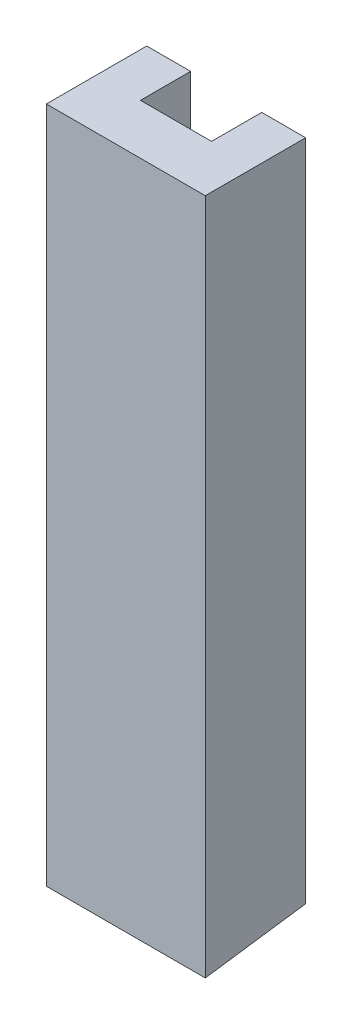
SolidWorks part; units mm, degrees
ref_plane "Front Plane" through (0, 0, 0) normal (0, 0, 1) x (1, 0, 0)
ref_plane "Top Plane" through (0, 0, 0) normal (0, 1, 0) x (1, 0, 0)
ref_plane "Right Plane" through (0, 0, 0) normal (1, 0, 0) x (0, 0, -1)
sketch "Sketch1" plane through (0, 0, 0) normal (0, 0, 1) x (1, 0, 0)
  line L1 (-9.7143, 13.1912) -> (9.2857, 13.1912)
  line L2 (-9.7143, 13.1912) -> (-9.7143, -67.8088)
  line L3 (-9.7143, -67.8088) -> (9.2857, -67.8088)
  line L4 (9.2857, 13.1912) -> (9.2857, -67.8088)
  dimension "D1" = 19
  dimension "D2" = 81
extrude "Boss-Extrude1" add sketch "Sketch1" along normal blind 12
sketch "Sketch2" plane through (0, 0, 0) normal (0, 0, -1) x (-1, 0, 0)
  line L0 (0.2143, 16.8694) -> (0.2143, -71.6226) construction
  line L5 (-9.2857, -67.8088) -> (-9.2857, 13.1912) construction
  line L6 (9.7143, 13.1912) -> (9.7143, -67.8088) construction
  line L7 (-9.2857, 13.1912) -> (9.7143, 13.1912) construction
  line L8 (-4.0357, 13.1912) -> (4.4643, 13.1912)
  line L9 (-4.0357, 13.1912) -> (-4.0357, -67.8088)
  line L10 (-4.0357, -67.8088) -> (4.4643, -67.8088)
  line L11 (4.4643, 13.1912) -> (4.4643, -67.8088)
  line L13 (9.7143, -67.8088) -> (-9.2857, -67.8088) construction
  dimension "D1" = 8.5
extrude "Cut-Extrude1" cut sketch "Sketch2" against normal blind 6
ref_plane "Plane1" through (0, -64.8416, -9.1129) normal (0, -0.9903, -0.1392) x (1, 0, 0)
sketch "Sketch3" plane through (0, -64.8416, -9.1129) normal (0, -0.9903, -0.1392) x (1, 0, 0)
  line L9 (-16.6295, 27.5301) -> (15.1549, 27.5301)
  line L10 (-16.6295, 27.5301) -> (-16.6295, 7.4455)
  line L11 (-16.6295, 7.4455) -> (15.1549, 7.4455)
  line L12 (15.1549, 27.5301) -> (15.1549, 7.4455)
extrude "Cut-Extrude2" cut sketch "Sketch3" along normal through all
